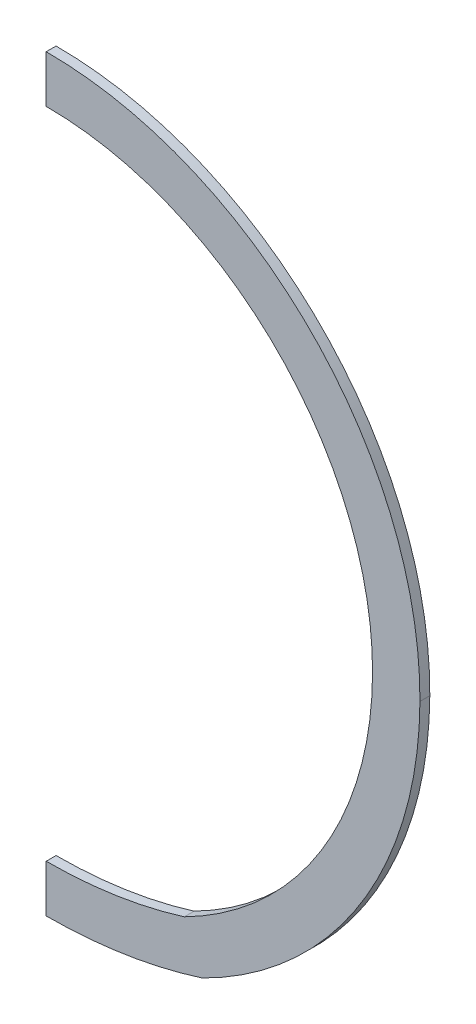
SolidWorks part; units mm, degrees
material "Balsa"
ref_plane "Front Plane" through (0, 0, 0) normal (0, 0, 1) x (1, 0, 0)
ref_plane "Top Plane" through (0, 0, 0) normal (0, 1, 0) x (1, 0, 0)
ref_plane "Right Plane" through (0, 0, 0) normal (1, 0, 0) x (0, 0, -1)
sketch "Sketch2" plane through (0, 0, 0) normal (0, 0, 1) x (1, 0, 0)
  line L0 (0, 0) -> (0.688, 245.4392) construction
  line L1 (-0.1309, -46.7153) -> (-0.2841, -101.3462) construction
  line L2 (0.0534, 19.05) -> (-169.3081, 19.05) construction
  line L3 (-72.7218, -93.726) -> (74.7111, -93.726) construction
  arc A1 (-120.0989, 19.05) -> (120.2036, 18.3433) centre (0.0534, 19.05) cw
  arc A2 (-120.0989, 19.05) -> (-50.0584, -93.726) centre (5.7147, 19.05) ccw
  arc A3 (-50.0584, -93.726) -> (50.1388, -93.726) centre (0.0402, 63.5) ccw
  arc A4 (120.2036, 18.3433) -> (50.1388, -93.726) centre (-5.6406, 19.0835) cw
  arc A5 (-104.8589, 19.05) -> (104.9639, 18.4329) centre (0.0534, 19.05) cw
  arc A6 (104.9639, 18.4329) -> (44.4049, -79.5534) centre (-5.6406, 19.0835) cw
  arc A7 (-44.324, -79.5535) -> (44.4049, -79.5534) centre (0.0402, 63.5) ccw
  arc A8 (-104.8589, 19.05) -> (-44.324, -79.5535) centre (5.7147, 19.05) ccw
  spline S0 degree 3 poles (-5521.0274, 5583.2546) (-1226.7801, 553.2855) (-196.9505, -260.8007) (69.4764, -82.4823) (75.8596, -77.7331) (81.7614, -72.3621) (85.2966, -68.8071) (85.996, -68.0862) (87.3792, -66.6243) (88.0639, -65.8824) (90.0847, -63.6371) (91.3894, -62.1126) (95.1787, -57.4581) (97.5389, -54.2471) (101.9343, -47.6137) (103.9694, -44.1914) (106.7765, -38.8981) (107.6712, -37.107) (109.3772, -33.4707) (110.1904, -31.6207) (112.481, -26.0415) (113.8153, -22.2742) (116.1105, -14.6467) (117.0712, -10.7866) (118.62, -2.9737) (119.208, 0.9791) (119.8028, 6.9796) (119.953, 8.9949) (120.1541, 13.0067) (120.2055, 15.0081) (120.2151, 20.9991) (119.8425, 28.9519) (118.7088, 36.835) (117.5685, 42.7208) (117.1399, 44.6783) (116.1841, 48.5842) (115.6559, 50.5346) (113.94, 56.3082) (112.6165, 60.0751) (109.6192, 67.4485) (107.9453, 71.055) (104.2453, 78.1066) (102.2192, 81.5518) (99.4588, 85.754) (98.8945, 86.5903) (97.7468, 88.2466) (97.1639, 89.0659) (95.3883, 91.4977) (94.1686, 93.0841) (90.4034, 97.7402) (87.752, 100.7072) (82.1689, 106.369) (79.2371, 109.0639) (74.6247, 112.8977) (73.0514, 114.1408) (70.6363, 115.9521) (69.821, 116.5478) (68.1799, 117.7153) (67.3537, 118.2875) (63.1947, 121.0918) (59.7778, 123.1535) (52.769, 126.9212) (49.1769, 128.6272) (41.816, 131.6806) (38.0473, 133.028) (33.2217, 134.4796) (32.2518, 134.758) (30.3116, 135.2882) (29.34, 135.5404) (26.4206, 136.2591) (24.4685, 136.6873) (18.5945, 137.8219) (14.6552, 138.3782) (6.7301, 139.0933) (2.7444, 139.252) (-2.2675, 139.1959) (-3.2714, 139.172) (-5.2821, 139.0983) (-6.2905, 139.0484) (-9.3072, 138.8606) (-11.3068, 138.6846) (-17.272, 138.0072) (-25.1357, 136.7069) (-32.823, 134.6274) (-38.5216, 132.7724) (-40.41, 132.1048) (-44.1641, 130.6694) (-46.0326, 129.9002) (-465.435, -55.3606) (264.7727, -2591.6725) (2155.1784, -7505.3224) knots -2.450405 -2.450405 -2.450405 -2.450405 0.03125 0.03125 0.0625 0.09375 0.09375 0.101563 0.101563 0.109375 0.109375 0.125 0.125 0.15625 0.15625 0.1875 0.1875 0.203125 0.203125 0.21875 0.21875 0.25 0.25 0.28125 0.28125 0.3125 0.3125 0.328125 0.328125 0.34375 0.34375 0.375 0.40625 0.40625 0.421875 0.421875 0.4375 0.4375 0.46875 0.46875 0.5 0.5 0.53125 0.53125 0.539063 0.539063 0.546875 0.546875 0.5625 0.5625 0.59375 0.59375 0.625 0.625 0.640625 0.640625 0.648438 0.648438 0.65625 0.65625 0.6875 0.6875 0.71875 0.71875 0.75 0.75 0.757813 0.757813 0.765625 0.765625 0.78125 0.78125 0.8125 0.8125 0.84375 0.84375 0.851563 0.851563 0.859375 0.859375 0.875 0.875 0.90625 0.9375 0.9375 0.953125 0.953125 0.96875 0.96875 4.508313 4.508313 4.508313 4.508313 only from (55.8537, -90.8749) to (-58.6671, 123.6507)
  spline S1 degree 3 poles (55.8537, -90.8749) (59.4151, -88.9779) (62.8499, -86.9173) (69.4764, -82.4823) (75.8596, -77.7331) (81.7614, -72.3621) (85.2966, -68.8071) (85.996, -68.0862) (87.3792, -66.6243) (88.0639, -65.8824) (90.0847, -63.6371) (91.3894, -62.1126) (95.1787, -57.4581) (97.5389, -54.2471) (101.9343, -47.6137) (103.9694, -44.1914) (106.7765, -38.8981) (107.6712, -37.107) (109.3772, -33.4707) (110.1904, -31.6207) (112.481, -26.0415) (113.8153, -22.2742) (116.1105, -14.6467) (117.0712, -10.7866) (118.62, -2.9737) (119.208, 0.9791) (119.8028, 6.9796) (119.953, 8.9949) (120.1541, 13.0067) (120.2055, 15.0081) (120.2151, 20.9991) (119.8425, 28.9519) (118.7088, 36.835) (117.5685, 42.7208) (117.1399, 44.6783) (116.1841, 48.5842) (115.6559, 50.5346) (113.94, 56.3082) (112.6165, 60.0751) (109.6192, 67.4485) (107.9453, 71.055) (104.2453, 78.1066) (102.2192, 81.5518) (99.4588, 85.754) (98.8945, 86.5903) (97.7468, 88.2466) (97.1639, 89.0659) (95.3883, 91.4977) (94.1686, 93.0841) (90.4034, 97.7402) (87.752, 100.7072) (82.1689, 106.369) (79.2371, 109.0639) (74.6247, 112.8977) (73.0514, 114.1408) (70.6363, 115.9521) (69.821, 116.5478) (68.1799, 117.7153) (67.3537, 118.2875) (63.1947, 121.0918) (59.7778, 123.1535) (52.769, 126.9212) (49.1769, 128.6272) (41.816, 131.6806) (38.0473, 133.028) (33.2217, 134.4796) (32.2518, 134.758) (30.3116, 135.2882) (29.34, 135.5404) (26.4206, 136.2591) (24.4685, 136.6873) (18.5945, 137.8219) (14.6552, 138.3782) (6.7301, 139.0933) (2.7444, 139.252) (-2.2675, 139.1959) (-3.2714, 139.172) (-5.2821, 139.0983) (-6.2905, 139.0484) (-9.3072, 138.8606) (-11.3068, 138.6846) (-17.272, 138.0072) (-25.1357, 136.7069) (-32.823, 134.6274) (-38.5216, 132.7724) (-40.41, 132.1048) (-44.1641, 130.6694) (-46.0326, 129.9002) (-51.5624, 127.4576) (-55.1595, 125.6458) (-58.6671, 123.6507) knots 0 0 0 0 0.03125 0.03125 0.0625 0.09375 0.09375 0.101563 0.101563 0.109375 0.109375 0.125 0.125 0.15625 0.15625 0.1875 0.1875 0.203125 0.203125 0.21875 0.21875 0.25 0.25 0.28125 0.28125 0.3125 0.3125 0.328125 0.328125 0.34375 0.34375 0.375 0.40625 0.40625 0.421875 0.421875 0.4375 0.4375 0.46875 0.46875 0.5 0.5 0.53125 0.53125 0.539063 0.539063 0.546875 0.546875 0.5625 0.5625 0.59375 0.59375 0.625 0.625 0.640625 0.640625 0.648438 0.648438 0.65625 0.65625 0.6875 0.6875 0.71875 0.71875 0.75 0.75 0.757813 0.757813 0.765625 0.765625 0.78125 0.78125 0.8125 0.8125 0.84375 0.84375 0.851563 0.851563 0.859375 0.859375 0.875 0.875 0.90625 0.9375 0.9375 0.953125 0.953125 0.96875 0.96875 1 1 1 1 construction
  spline S2 degree 3 poles (5694.5744, -5369.3669) (1292.3799, -516.6509) (187.1926, 314.492) (-76.9523, 111.0297) (-81.0984, 107.3558) (-85.9766, 102.3921) (-86.9369, 101.3807) (-88.8267, 99.3202) (-89.7577, 98.2691) (-92.4915, 95.0728) (-94.2304, 92.8907) (-99.2026, 86.1952) (-102.1931, 81.5333) (-106.1993, 74.2476) (-107.4545, 71.77) (-109.2154, 67.9791) (-109.782, 66.7031) (-110.874, 64.1258) (-111.4002, 62.8224) (-113.9097, 56.2871) (-115.5417, 50.9767) (-118.0823, 40.1978) (-118.9908, 34.7292) (-119.6657, 27.7928) (-119.7775, 26.4005) (-119.9543, 23.6055) (-120.0192, 22.2016) (-120.1418, 18.0057) (-120.1286, 15.2199) (-119.8102, 6.8959) (-119.2278, 1.3912) (-117.8014, -6.7994) (-117.2335, -9.5184) (-116.2404, -13.58) (-115.8858, -14.9311) (-115.1288, -17.6274) (-114.7258, -18.9739) (-112.6063, -25.6411) (-108.5276, -35.9696) (-103.1136, -45.6397) (-99.3011, -51.4722) (-98.5171, -52.628) (-96.9053, -54.9182) (-96.0765, -56.0537) (-93.5433, -59.4015) (-91.7865, -61.5635) (-86.3167, -67.8444) (-82.4051, -71.759) (-76.1398, -77.2217) (-73.9848, -78.9742) (-70.6503, -81.498) (-69.5218, -82.3217) (-67.2303, -83.9337) (-66.0665, -84.7222) (540.7318, -480.5341) (3882.3497, 5108.7967) (222.2795, -4616.5222) knots -3.63779 -3.63779 -3.63779 -3.63779 0.0625 0.0625 0.125 0.125 0.140625 0.140625 0.15625 0.15625 0.1875 0.1875 0.25 0.25 0.28125 0.28125 0.296875 0.296875 0.3125 0.3125 0.375 0.375 0.4375 0.4375 0.453125 0.453125 0.46875 0.46875 0.5 0.5 0.5625 0.5625 0.59375 0.59375 0.609375 0.609375 0.625 0.625 0.6875 0.75 0.75 0.765625 0.765625 0.78125 0.78125 0.8125 0.8125 0.875 0.875 0.90625 0.90625 0.921875 0.921875 0.9375 0.9375 9.012836 9.012836 9.012836 9.012836 only from (-58.6671, 123.6507) to (-50.3455, -93.5936)
  spline S3 degree 3 poles (-4578.1193, 6360.5009) (1102.8247, -3189.0685) (1357.3206, -1629.0846) (-2110.3169, 7551.2134) knots -196.711406 -196.711406 -196.711406 -196.711406 209.883914 209.883914 209.883914 209.883914 only from (49.819, -93.8744) to (55.8537, -90.8749)
  spline S4 degree 3 poles (49.819, -93.8744) (51.8584, -92.9316) (53.87, -91.9317) (55.8537, -90.8749) knots 0 0 0 0 1 1 1 1 construction
  spline S5 degree 3 poles (-58.6671, 123.6507) (-63.5487, 120.874) (-68.1774, 117.7887) (-76.9523, 111.0297) (-81.0984, 107.3558) (-85.9766, 102.3921) (-86.9369, 101.3807) (-88.8267, 99.3202) (-89.7577, 98.2691) (-92.4915, 95.0728) (-94.2304, 92.8907) (-99.2026, 86.1952) (-102.1931, 81.5333) (-106.1993, 74.2476) (-107.4545, 71.77) (-109.2154, 67.9791) (-109.782, 66.7031) (-110.874, 64.1258) (-111.4002, 62.8224) (-113.9097, 56.2871) (-115.5417, 50.9767) (-118.0823, 40.1978) (-118.9908, 34.7292) (-119.6657, 27.7928) (-119.7775, 26.4005) (-119.9543, 23.6055) (-120.0192, 22.2016) (-120.1418, 18.0057) (-120.1286, 15.2199) (-119.8102, 6.8959) (-119.2278, 1.3912) (-117.8014, -6.7994) (-117.2335, -9.5184) (-116.2404, -13.58) (-115.8858, -14.9311) (-115.1288, -17.6274) (-114.7258, -18.9739) (-112.6063, -25.6411) (-108.5276, -35.9696) (-103.1136, -45.6397) (-99.3011, -51.4722) (-98.5171, -52.628) (-96.9053, -54.9182) (-96.0765, -56.0537) (-93.5433, -59.4015) (-91.7865, -61.5635) (-86.3167, -67.8444) (-82.4051, -71.759) (-76.1398, -77.2217) (-73.9848, -78.9742) (-70.6503, -81.498) (-69.5218, -82.3217) (-67.2303, -83.9337) (-66.0665, -84.7222) (-60.2073, -88.5441) (-55.3561, -91.2432) (-50.3455, -93.5936) knots 0 0 0 0 0.0625 0.0625 0.125 0.125 0.140625 0.140625 0.15625 0.15625 0.1875 0.1875 0.25 0.25 0.28125 0.28125 0.296875 0.296875 0.3125 0.3125 0.375 0.375 0.4375 0.4375 0.453125 0.453125 0.46875 0.46875 0.5 0.5 0.5625 0.5625 0.59375 0.59375 0.609375 0.609375 0.625 0.625 0.6875 0.75 0.75 0.765625 0.765625 0.78125 0.78125 0.8125 0.8125 0.875 0.875 0.90625 0.90625 0.921875 0.921875 0.9375 0.9375 1 1 1 1 construction
  spline S6 degree 3 poles (-1759.0643, 7695.5768) (129.301, 75.0658) (104.9025, -75.6984) (45.8458, -95.3665) (44.8322, -95.6594) (41.7708, -96.4587) (39.7032, -96.8873) (35.5384, -97.6293) (33.4392, -97.9405) (29.2422, -98.4783) (27.1412, -98.7049) (20.8322, -99.2882) (16.6185, -99.55) (8.1799, -99.8877) (3.9548, -99.9623) (-4.5058, -99.9387) (-8.734, -99.8405) (-17.1695, -99.4557) (-21.3793, -99.1705) (-27.6778, -98.553) (-29.7745, -98.3152) (-33.9608, -97.7556) (-36.0504, -97.4344) (-39.177, -96.8603) (-40.2191, -96.653) (-42.292, -96.1992) (-43.3225, -95.953) (-45.3676, -95.407) (-46.3821, -95.1076) (-105.8729, -74.9194) (-124.4058, 77.5041) (2082.3243, 7613.4914) knots -1.777254 -1.777254 -1.777254 -1.777254 0.03125 0.03125 0.0625 0.0625 0.125 0.125 0.1875 0.1875 0.25 0.25 0.375 0.375 0.5 0.5 0.625 0.625 0.75 0.75 0.8125 0.8125 0.875 0.875 0.90625 0.90625 0.9375 0.9375 0.96875 0.96875 2.792352 2.792352 2.792352 2.792352 only from (49.8185, -93.8746) to (-50.3451, -93.5938)
  spline S7 degree 3 poles (49.8185, -93.8746) (48.8452, -94.325) (47.8521, -94.6984) (45.8458, -95.3665) (44.8322, -95.6594) (41.7708, -96.4587) (39.7032, -96.8873) (35.5384, -97.6293) (33.4392, -97.9405) (29.2422, -98.4783) (27.1412, -98.7049) (20.8322, -99.2882) (16.6185, -99.55) (8.1799, -99.8877) (3.9548, -99.9623) (-4.5058, -99.9387) (-8.734, -99.8405) (-17.1695, -99.4557) (-21.3793, -99.1705) (-27.6778, -98.553) (-29.7745, -98.3152) (-33.9608, -97.7556) (-36.0504, -97.4344) (-39.177, -96.8603) (-40.2191, -96.653) (-42.292, -96.1992) (-43.3225, -95.953) (-45.3676, -95.407) (-46.3821, -95.1076) (-48.3867, -94.4274) (-49.3773, -94.0483) (-50.3451, -93.5938) knots 0 0 0 0 0.03125 0.03125 0.0625 0.0625 0.125 0.125 0.1875 0.1875 0.25 0.25 0.375 0.375 0.5 0.5 0.625 0.625 0.75 0.75 0.8125 0.8125 0.875 0.875 0.90625 0.90625 0.9375 0.9375 0.96875 0.96875 1 1 1 1 construction
  spline S8 degree 1 poles (44.4895, -82.3468) (49.8828, -79.6661) knots 0 0 1 1 construction
  spline S9 degree 1 poles (49.8828, -79.6661) (-52.388, 112.6115) knots 0 0 1 1 construction
  spline S10 degree 1 poles (-52.388, 112.6115) (-44.952, -82.0958) knots 0 0 1 1 construction
  spline S11 degree 3 poles (44.4895, -82.3468) (44.9451, -82.1361) (45.8533, -81.7084) (47.2062, -81.0479) (48.5497, -80.3682) (49.4396, -79.9022) (49.8828, -79.6661) knots 0 0 0 0 0.250007 0.500014 0.750021 1.000028 1.000028 1.000028 1.000028 construction
  spline S12 degree 3 poles (49.8828, -79.6661) (51.4682, -78.8216) (54.6039, -77.0481) (60.6329, -73.2256) (67.7713, -67.9145) (75.6946, -60.7068) (85.376, -49.946) (92.2499, -39.5527) (97.0635, -29.9209) (99.9774, -23.2906) (102.9687, -14.8438) (105.5551, -4.452) (106.8747, 4.4138) (107.4138, 11.642) (107.598, 18.8242) (107.1791, 27.7507) (105.6575, 38.3493) (103.0737, 48.9109) (99.5091, 59.0529) (95.0071, 68.7524) (90.4672, 76.4728) (86.3465, 82.4205) (79.7918, 90.9419) (71.0678, 99.805) (59.5047, 108.4813) (50.3361, 114.0108) (40.7123, 118.5824) (32.2831, 121.5955) (25.3334, 123.4944) (18.366, 125.0225) (9.571, 126.2643) (-1.0997, 126.6912) (-11.9104, 126.0185) (-22.4327, 124.2743) (-36.1547, 120.5693) (-46.1487, 116.1604) (-52.388, 112.6115) knots 0 0 0 0 0.015625 0.03125 0.0625 0.09375 0.125 0.1875 0.203125 0.21875 0.25 0.28125 0.3125 0.328125 0.34375 0.375 0.40625 0.4375 0.46875 0.5 0.53125 0.546875 0.5625 0.625 0.65625 0.6875 0.71875 0.75 0.765625 0.78125 0.8125 0.84375 0.875 0.90625 0.9375 1 1 1 1 construction
  spline S13 degree 3 poles (-52.388, 112.6115) (-54.5585, 111.3769) (-58.8261, 108.7475) (-66.8816, 102.9693) (-76.1597, 94.757) (-85.9932, 83.258) (-92.681, 72.8203) (-97.1816, 63.9424) (-101.112, 54.6656) (-104.776, 42.7383) (-106.8137, 30.488) (-107.4512, 20.4245) (-107.4028, 10.4189) (-106.3564, 0.5368) (-104.3212, -9.2152) (-101.5955, -18.9231) (-97.0158, -30.5128) (-90.9605, -41.334) (-85.1677, -49.567) (-78.8706, -57.3154) (-71.8665, -64.3232) (-64.1621, -70.5906) (-57.9948, -74.9291) (-51.5954, -78.7902) (-47.193, -81.0446) (-44.952, -82.0958) knots 0 0 0 0 0.03125 0.0625 0.125 0.1875 0.25 0.28125 0.3125 0.375 0.4375 0.46875 0.5 0.5625 0.59375 0.625 0.6875 0.75 0.78125 0.8125 0.875 0.90625 0.9375 0.96875 1 1 1 1 construction
  spline S14 degree 1 poles (44.4849, -82.3489) (-44.9469, -82.0982) knots 0 0 1 1 construction
  spline S15 degree 3 poles (44.4849, -82.3489) (44.3746, -82.3999) (44.1627, -82.4934) (43.6492, -82.7012) (42.8561, -82.9839) (41.7841, -83.3184) (40.2245, -83.7477) (38.1103, -84.2445) (35.4106, -84.7656) (32.6063, -85.224) (28.7759, -85.7537) (23.885, -86.2821) (17.9201, -86.7432) (11.8971, -87.0512) (5.8396, -87.2261) (-2.2666, -87.2864) (-10.3738, -87.0974) (-18.3985, -86.6419) (-24.3556, -86.1481) (-29.2377, -85.5934) (-33.056, -85.0443) (-35.8555, -84.5718) (-38.5671, -84.0318) (-40.6899, -83.5223) (-42.2517, -83.0828) (-43.3238, -82.7417) (-44.1147, -82.4546) (-44.6269, -82.2439) (-44.8373, -82.1497) (-44.9469, -82.0982) knots 0 0 0 0 0.007812 0.015625 0.03125 0.046875 0.0625 0.09375 0.125 0.15625 0.1875 0.25 0.3125 0.375 0.4375 0.5 0.625 0.6875 0.75 0.8125 0.84375 0.875 0.90625 0.9375 0.953125 0.96875 0.984375 0.992188 1 1 1 1 construction
  point P12 (-0.2802, -99.9505)
  dimension "D3" = 19.05
  dimension "D4" = 93.726
  dimension "D5" = 63.5
  dimension "D6" = 15.24
  dimension "D1" = 12.7
  dimension "D2" = 12.7
extrude "Boss-Extrude1" add sketch "Sketch2" along normal mid plane 3.175
sketch "Sketch3" plane through (0, 0, 0) normal (1, 0, 0) x (0, 0, -1)
  line L1 (-100.0568, 212.3798) -> (108.5889, 212.3798)
  line L2 (-100.0568, 212.3798) -> (-100.0568, -170.6472)
  line L3 (-100.0568, -170.6472) -> (108.5889, -170.6472)
  line L4 (108.5889, 212.3798) -> (108.5889, -170.6472)
extrude "Cut-Extrude1" cut sketch "Sketch3" against normal through all
